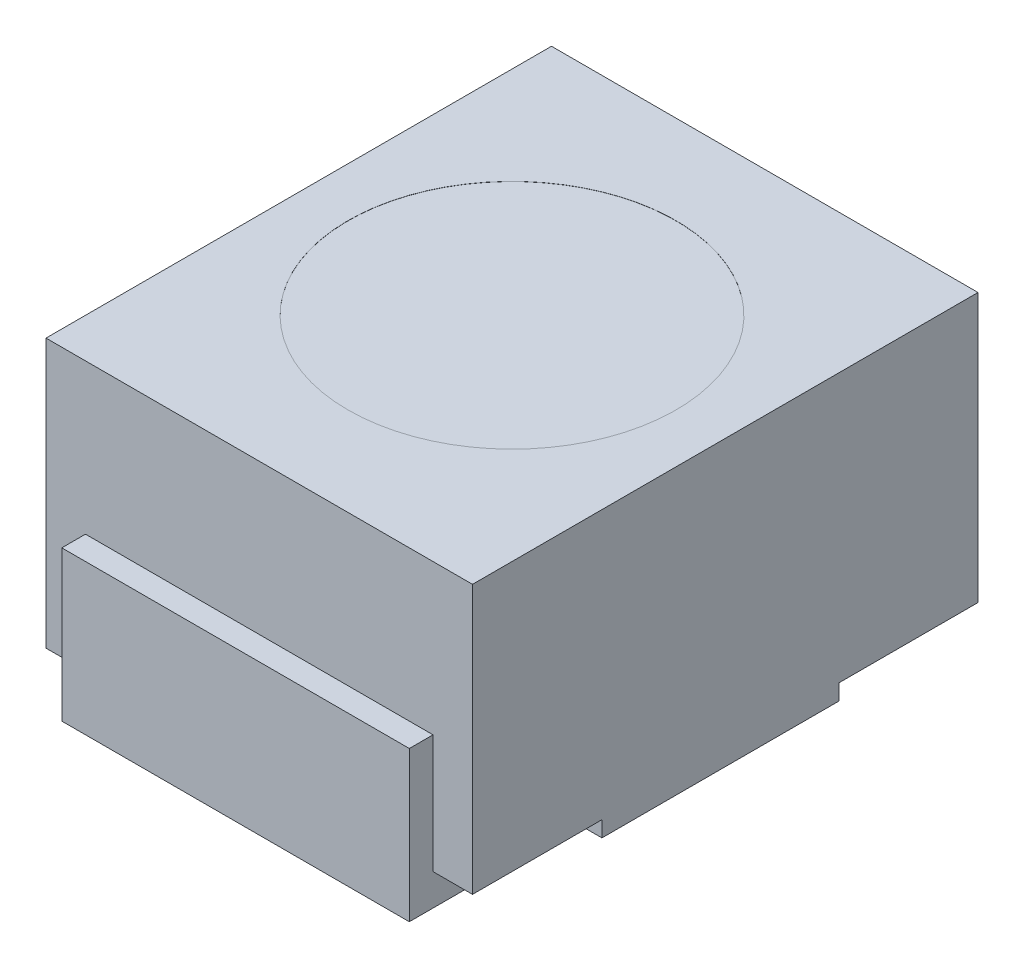
SolidWorks part; units mm, degrees
ref_plane "Front Plane" through (0, 0, 0) normal (0, 0, 1) x (1, 0, 0)
ref_plane "Top Plane" through (0, 0, 0) normal (0, 1, 0) x (1, 0, 0)
ref_plane "Right Plane" through (0, 0, 0) normal (1, 0, 0) x (0, 0, -1)
sketch "Sketch1" plane through (0, 0, 0) normal (0, 1, 0) x (1, 0, 0)
  line L1 (-1.35, -1.6) -> (1.35, -1.6)
  line L2 (-1.35, -1.6) -> (-1.35, 1.6)
  line L3 (-1.35, 1.6) -> (1.35, 1.6)
  line L4 (1.35, -1.6) -> (1.35, 1.6)
  line L5 (-1.35, -1.6) -> (1.35, 1.6) construction
  line L6 (-1.35, 1.6) -> (1.35, -1.6) construction
  point P0 (0, 0)
  dimension "D1" = 2.7
  dimension "D2" = 3.2
extrude "Boss-Extrude1" add sketch "Sketch1" along normal blind 1.9
sketch "Sketch4" plane through (0, 0, 0) normal (0, -1, 0) x (1, 0, 0)
  line L1 (-1.1, 1.75) -> (1.1, 1.75)
  line L2 (-1.1, 1.75) -> (-1.1, 1.6)
  line L3 (-1.1, 1.6) -> (1.1, 1.6)
  line L4 (1.1, 1.75) -> (1.1, 1.6)
  line L5 (-1.1, -1.6) -> (1.1, -1.6)
  line L6 (-1.1, -1.6) -> (-1.1, -1.75)
  line L7 (-1.1, -1.75) -> (1.1, -1.75)
  line L8 (1.1, -1.6) -> (1.1, -1.75)
extrude "Boss-Extrude3" add sketch "Sketch4" against normal blind 0.95
sketch "Sketch5" plane through (0, 0, 0) normal (0, -1, 0) x (1, 0, 0)
  line L0 (-1.35, -1.6) -> (-1.35, 1.6) construction
  line L1 (-1.35, 1.3971) -> (1.35, 1.3971)
  line L2 (-1.35, 1.3971) -> (-1.35, -1.4313)
  line L3 (-1.35, -1.4313) -> (1.35, -1.4313)
  line L4 (1.35, 1.3971) -> (1.35, -1.4313)
  line L5 (1.35, 1.6) -> (1.35, -1.6) construction
extrude "Cut-Extrude1" cut sketch "Sketch5" against normal blind 0.2
sketch "Sketch6" plane through (0, 0.2, 0) normal (0, -1, 0) x (1, 0, 0)
  line L0 (-1.35, 1.3971) -> (-1.35, -1.4313) construction
  line L1 (-1.35, 0.7807) -> (1.35, 0.7807)
  line L2 (-1.35, 0.7807) -> (-1.35, -0.7193)
  line L3 (-1.35, -0.7193) -> (1.35, -0.7193)
  line L4 (1.35, 0.7807) -> (1.35, -0.7193)
  line L5 (1.35, -1.4313) -> (1.35, 1.3971) construction
  dimension "D1" = 1.5
extrude "Boss-Extrude4" add sketch "Sketch6" along normal blind 0.1
sketch "Sketch7" plane through (0, 0.2, 0) normal (0, -1, 0) x (1, 0, 0)
  line L1 (-1.1, 1.6) -> (-1.4324, 1.6)
  line L2 (-1.1, 1.6) -> (-1.1, 1.3069)
  line L3 (-1.1, 1.3069) -> (-1.4324, 1.3069)
  line L4 (-1.4324, 1.6) -> (-1.4324, 1.3069)
  line L5 (1.1, 1.6) -> (1.6379, 1.6)
  line L6 (1.1, 1.6) -> (1.1, 1.2384)
  line L7 (1.1, 1.2384) -> (1.6379, 1.2384)
  line L8 (1.6379, 1.6) -> (1.6379, 1.2384)
  line L9 (-1.35, -1.6) -> (-1.1, -1.6)
  line L10 (-1.35, -1.6) -> (-1.35, -1.2099)
  line L11 (-1.35, -1.2099) -> (-1.1, -1.2099)
  line L12 (-1.1, -1.6) -> (-1.1, -1.2099)
  line L13 (1.1, -1.6) -> (1.5637, -1.6)
  line L14 (1.1, -1.6) -> (1.1, -1.2099)
  line L15 (1.1, -1.2099) -> (1.5637, -1.2099)
  line L16 (1.5637, -1.6) -> (1.5637, -1.2099)
extrude "Cut-Extrude3" cut sketch "Sketch7" along normal through all
sketch "Sketch8" plane through (0, 0.2, 0) normal (0, -1, 0) x (1, 0, 0)
  line L0 (1.1, 1.6) -> (1.1, 1.3971) construction
  line L1 (-1.1, 1.3971) -> (1.1, 1.3971)
  line L2 (-1.1, 1.3971) -> (-1.1, 0.9416)
  line L3 (-1.1, 0.9416) -> (1.1, 0.9416)
  line L4 (1.1, 1.3971) -> (1.1, 0.9416)
  line L6 (-1.1, -1.4313) -> (1.1, -1.4313)
  line L7 (-1.1, -1.4313) -> (-1.1, -0.856)
  line L8 (-1.1, -0.856) -> (1.1, -0.856)
  line L9 (1.1, -1.4313) -> (1.1, -0.856)
extrude "Boss-Extrude5" add sketch "Sketch8" along normal up to surface (0.2 mm away) up to face at (0, 0, -1.5907)
sketch "Sketch9" plane through (0, 1.9, 0) normal (0, 1, 0) x (1, 0, 0)
  circle A0 centre (0, 0) radius 1.0382
extrude "Cut-Extrude4" cut sketch "Sketch9" against normal blind 0.001
